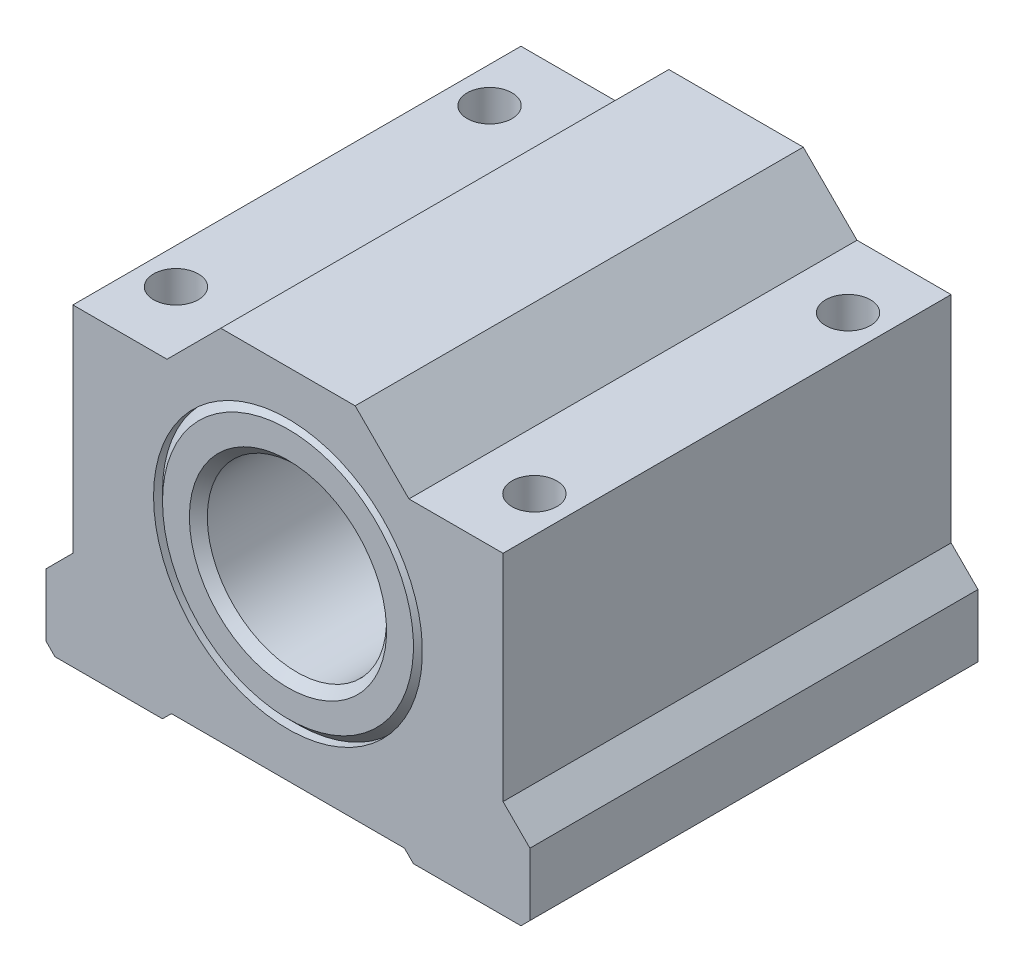
SolidWorks part; units mm, degrees
ref_plane "Ön Düzlem" through (0, 0, 0) normal (0, 0, 1) x (1, 0, 0)
ref_plane "Üst Düzlem" through (0, 0, 0) normal (0, 1, 0) x (1, 0, 0)
ref_plane "Sağ Düzlem" through (0, 0, 0) normal (1, 0, 0) x (0, 0, -1)
sketch "Çizim1" plane through (0, 0, 0) normal (0, 0, 1) x (1, 0, 0)
  line L1 (-24, -17) -> (24, -17)
  line L2 (-24, -17) -> (-24, 17)
  line L3 (-24, 17) -> (24, 17)
  line L4 (24, -17) -> (24, 17)
  line L5 (-24, -17) -> (24, 17) construction
  line L6 (-24, 17) -> (24, -17) construction
  point P0 (0, 0)
  dimension "D1" = 48
  dimension "D2" = 34
extrude "Yükseklik-Ekstrüzyon1" add sketch "Çizim1" along normal blind 50
sketch "Çizim2" plane through (0, 0, 50) normal (0, 0, 1) x (1, 0, 0)
  line L0 (-24, -17) -> (24, -17) construction
  line L1 (-27, -7) -> (-13, -7)
  line L2 (-27, -7) -> (-27, -18)
  line L3 (-27, -18) -> (-13, -18)
  line L4 (-13, -7) -> (-13, -18)
  line L5 (13, -7) -> (27, -7)
  line L6 (13, -7) -> (13, -18)
  line L7 (13, -18) -> (27, -18)
  line L8 (27, -7) -> (27, -18)
  line L9 (-24, 17) -> (-24, -17) construction
  line L10 (-13.5, 17) -> (13.5, 17)
  line L11 (24, 17) -> (-24, 17) construction
  line L12 (13.5, 17) -> (7.5, 23)
  line L13 (7.5, 23) -> (-7.5, 23)
  line L14 (-7.5, 23) -> (-13.5, 17)
  line L15 (0, 23) -> (0, -5.2264) construction
  dimension "D1" = 14
  dimension "D2" = 11
  dimension "D3" = 14
  dimension "D4" = 11
  dimension "D5" = 54
  dimension "D6" = 1
  dimension "D7" = 3
  dimension "D8" = 1
  dimension "D9" = 27
  dimension "D10" = 15
  dimension "D11" = 6
  dimension "D12" = 10.5
extrude "Yükseklik-Ekstrüzyon2" add sketch "Çizim2" against normal blind 50
sketch "Çizim3" plane through (0, 0, 0) normal (0, 0, -1) x (-1, 0, 0)
  line L1 (-7.5, 23) -> (7.5, 23) construction
  circle A0 centre (0, 3) radius 15
  dimension "D1" = 30
  dimension "D2" = 20
extrude "Kes-Ekstrüzyon1" cut sketch "Çizim3" against normal blind 50
sketch "Çizim4" plane through (0, 0, 0) normal (0, 0, -1) x (-1, 0, 0)
  circle A0 centre (0, 3) radius 15 construction
  circle A1 centre (0, 3) radius 15
  circle A2 centre (0, 3) radius 10
  dimension "D1" = 20
extrude "Yükseklik-Ekstrüzyon3" add sketch "Çizim4" against normal blind 50 separate body
sketch "Çizim5" plane through (0, -18, 0) normal (0, -1, 0) x (1, 0, 0)
  line L0 (13, 50) -> (27, 50) construction
  line L1 (27, 0) -> (27, 50) construction
  circle A0 centre (-20, 42.5) radius 2.5
  circle A1 centre (-20, 7.5) radius 2.5
  circle A2 centre (20, 7.5) radius 2.5
  circle A3 centre (20, 42.5) radius 2.5
  dimension "D1" = 5
  dimension "D2" = 5
  dimension "D3" = 5
  dimension "D4" = 5
  dimension "D5" = 35
  dimension "D6" = 40
  dimension "D7" = 7.5
  dimension "D8" = 7
extrude "Kes-Ekstrüzyon2" cut sketch "Çizim5" against normal blind 50
chamfer "Pah1" distance 1 angle 45 4 edges at (-27, -18, 25) (27, -18, 25) (13, -18, 25) (-13, -18, 25)
chamfer "Pah2" distance 3 angle 45 2 edges at (-27, -7, 25) (27, -7, 25)
chamfer "Pah3" distance 1 angle 45 4 edges at (-15, 3, 0) (-10, 3, 0) (-10, 3, 50) (-15, 3, 50)
